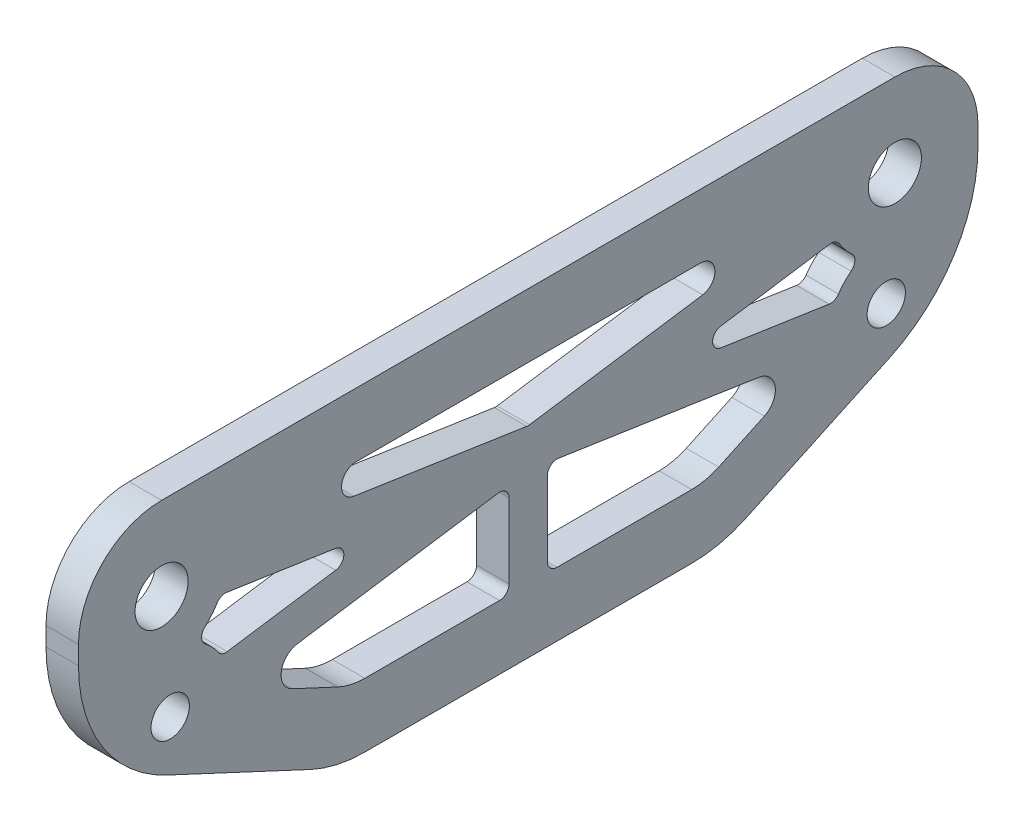
SolidWorks part; units mm, degrees
ref_plane "Front Plane" through (0, 0, 0) normal (0, 0, 1) x (1, 0, 0)
ref_plane "Top Plane" through (0, 0, 0) normal (0, 1, 0) x (1, 0, 0)
ref_plane "Right Plane" through (0, 0, 0) normal (1, 0, 0) x (0, 0, -1)
sketch "Sketch1" plane through (0, 0, 0) normal (1, 0, 0) x (0, 0, -1)
  line L0 (15, 12.5) -> (28.675, 12.5)
  line L1 (-15, -12.5) -> (15, -12.5)
  line L3 (-15, 12.5) -> (15, 12.5)
  line L5 (-15, -12.5) -> (15, 12.5) construction
  line L6 (-15, 12.5) -> (15, -12.5) construction
  line L8 (0, 12.5) -> (0, -12.5) construction
  line L10 (-15, 12.5) -> (-28.675, 12.5)
  line L11 (23.175, 175.0058) -> (23.175, -52.3942) construction
  line L13 (35.175, 6) -> (35.175, 4.5526)
  line L14 (28.2464, -6.3231) -> (15, -12.5)
  line L16 (-35.175, 6) -> (-35.175, 4.5526)
  line L17 (-28.2464, -6.3231) -> (-15, -12.5)
  arc A0 (28.675, 12.5) -> (35.175, 6) centre (28.675, 6) cw
  circle A1 centre (28.675, 6) radius 5.5 construction
  circle A2 centre (-28.675, 6) radius 5.5 construction
  arc A3 (-28.675, 12.5) -> (-35.175, 6) centre (-28.675, 6) ccw
  arc A4 (35.175, 4.5526) -> (28.2464, -6.3231) centre (23.175, 4.5526) cw
  circle A5 centre (28.675, 6) radius 2.075
  arc A6 (-35.175, 4.5526) -> (-28.2464, -6.3231) centre (-23.175, 4.5526) ccw
  circle A9 centre (-28.675, 6) radius 2.075
  circle A11 centre (28, -2.5) radius 1.5
  circle A12 centre (-28, -2.5) radius 1.5
  point P0 (0, 0)
  point P28 (0, 0)
  dimension "D1" = 11
  dimension "D2" = 1
  dimension "D3" = 4.15
  dimension "D4" = 3
  dimension "D6" = 25
  dimension "D8" = 12
  dimension "D5" = 25
  dimension "D7" = 30
  dimension "D9" = 28
  dimension "D10" = 2.5
extrude "Boss-Extrude1" add sketch "Sketch1" along normal blind 2.54
fillet "Fillet1" radius 10 2 edges at (1.27, -12.5, -15) (1.27, -12.5, 15)
sketch "Sketch2" plane through (0, 0, 0) normal (1, 0, 0) x (0, 0, -1)
  line L0 (-28.675, 6) -> (28, -2.5) construction
  line L10 (-28.675, -2.6012) -> (28.675, 6)
  line L11 (-28.675, 6) -> (28, -2.5)
  line L12 (-28.8975, 4.5166) -> (27.7775, -3.9834)
  line L13 (-28.4525, 7.4834) -> (28.2225, -1.0166)
  line L14 (-28.8975, 4.5166) -> (-28.4525, 7.4834)
  line L15 (27.7775, -3.9834) -> (28.2225, -1.0166)
  line L16 (-12.7831, -7.5) -> (12.7831, -7.5)
  line L17 (14.8961, -7.0315) -> (26.1333, -1.7916)
  line L18 (30.175, 4.5526) -> (30.175, 6)
  line L19 (28.675, 7.5) -> (-28.675, 7.5)
  line L20 (-30.175, 6) -> (-30.175, 4.5526)
  line L21 (-26.1333, -1.7916) -> (-14.8961, -7.0315)
  line L22 (-12.7831, -7.5) -> (12.7831, -7.5)
  line L23 (14.8961, -7.0315) -> (26.1333, -1.7916)
  line L24 (30.175, 4.5526) -> (30.175, 6)
  line L25 (28.675, 7.5) -> (-28.675, 7.5)
  line L26 (-30.175, 6) -> (-30.175, 4.5526)
  line L27 (-26.1333, -1.7916) -> (-14.8961, -7.0315)
  line L28 (-28.4525, -4.0846) -> (28.8975, 4.5166)
  line L29 (-28.8975, -1.1178) -> (28.4525, 7.4834)
  line L30 (-28.4525, -4.0846) -> (-28.8975, -1.1178)
  line L31 (28.8975, 4.5166) -> (28.4525, 7.4834)
  line L32 (0, -7.5) -> (0, 7.5) construction
  line L33 (0, 1.6994) -> (0, -7.5)
  line L34 (-1.5, 1.6994) -> (-1.5, -7.5)
  line L35 (1.5, 1.6994) -> (1.5, -7.5)
  line L36 (-1.5, 1.6994) -> (1.5, 1.6994)
  line L37 (-1.5, -7.5) -> (1.5, -7.5)
  arc A0 (-18.0527, -2.5249) -> (-18.4641, -5.3678) centre (-17.8302, -4.0083) ccw
  arc A1 (18.0527, -2.5249) -> (18.4641, -5.3678) centre (17.8302, -4.0083) cw
  circle A2 centre (-28, -2.5) radius 4.5
  circle A3 centre (-28, -2.5) radius 4.5
  circle A5 centre (28, -2.5) radius 4.5
  circle A6 centre (28, -2.5) radius 4.5
  circle A11 centre (-28.675, 6) radius 5.075
  arc A12 (12.7831, -7.5) -> (14.8961, -7.0315) centre (12.7831, -2.5) ccw
  arc A13 (26.1333, -1.7916) -> (30.175, 4.5526) centre (23.175, 4.5526) ccw
  arc A14 (30.175, 6) -> (28.675, 7.5) centre (28.675, 6) ccw
  arc A15 (-28.675, 7.5) -> (-30.175, 6) centre (-28.675, 6) ccw
  arc A16 (-30.175, 4.5526) -> (-26.1333, -1.7916) centre (-23.175, 4.5526) ccw
  arc A17 (-14.8961, -7.0315) -> (-12.7831, -7.5) centre (-12.7831, -2.5) ccw
  arc A18 (12.7831, -7.5) -> (14.8961, -7.0315) centre (12.7831, -2.5) ccw
  arc A19 (26.1333, -1.7916) -> (30.175, 4.5526) centre (23.175, 4.5526) ccw
  arc A20 (30.175, 6) -> (28.675, 7.5) centre (28.675, 6) ccw
  arc A21 (-28.675, 7.5) -> (-30.175, 6) centre (-28.675, 6) ccw
  arc A22 (-30.175, 4.5526) -> (-26.1333, -1.7916) centre (-23.175, 4.5526) ccw
  arc A23 (-14.8961, -7.0315) -> (-12.7831, -7.5) centre (-12.7831, -2.5) ccw
  circle A24 centre (-28.675, 6) radius 5.075
  circle A26 centre (28.675, 6) radius 5.075
  circle A27 centre (28.675, 6) radius 5.075
  arc A32 (13.477, 7.5) -> (13.6439, 5.2624) centre (13.477, 6.375) cw
  arc A33 (-13.477, 7.5) -> (-13.6439, 5.2624) centre (-13.477, 6.375) ccw
  dimension "D11" = 3
  dimension "D12" = 1.125
  dimension "D2" = 1.5
  dimension "D1" = 5
  dimension "D3" = 3
  dimension "D4" = 3
  dimension "D6" = 1.5
  dimension "D7" = 1.5
  dimension "D8" = 1.5
  dimension "D9" = 1.5
  dimension "D13" = 1.5
  dimension "D14" = 1.5
  dimension "D15" = 3
extrude "Cut-Extrude2" cut sketch "Sketch2" along normal through all contours A24 A3 L29 L12 | A27 L28 L13 A6 | L25 A33 L13 L29 A32 | A1 L12 L35 L22 | L28 A0 L22 L34 region at (0, 1.7005, 19.9688) region at (0, -4.2389, 9.1911) region at (0, 5.8357, 0) region at (0, -4.2389, -9.1911) region at (0, 1.7005, -19.9688)
fillet "Fillet2" radius 0.75 13 edges at (1.27, -7.5, -1.5) (1.27, 3.7975, -24.1028) (1.27, 1.6994, -10.1133) (1.27, 3.7975, 24.1028) (1.27, 3.2162, 0) (1.27, -0.0424, -1.5) (1.27, -7.5, 1.5) (1.27, -0.0424, 1.5) (1.27, 1.6994, 10.1133) (1.27, -0.3873, -24.0268) (1.27, 1.6002, -26.1457) (1.27, -0.3873, 24.0268) (1.27, 1.6002, 26.1457)
